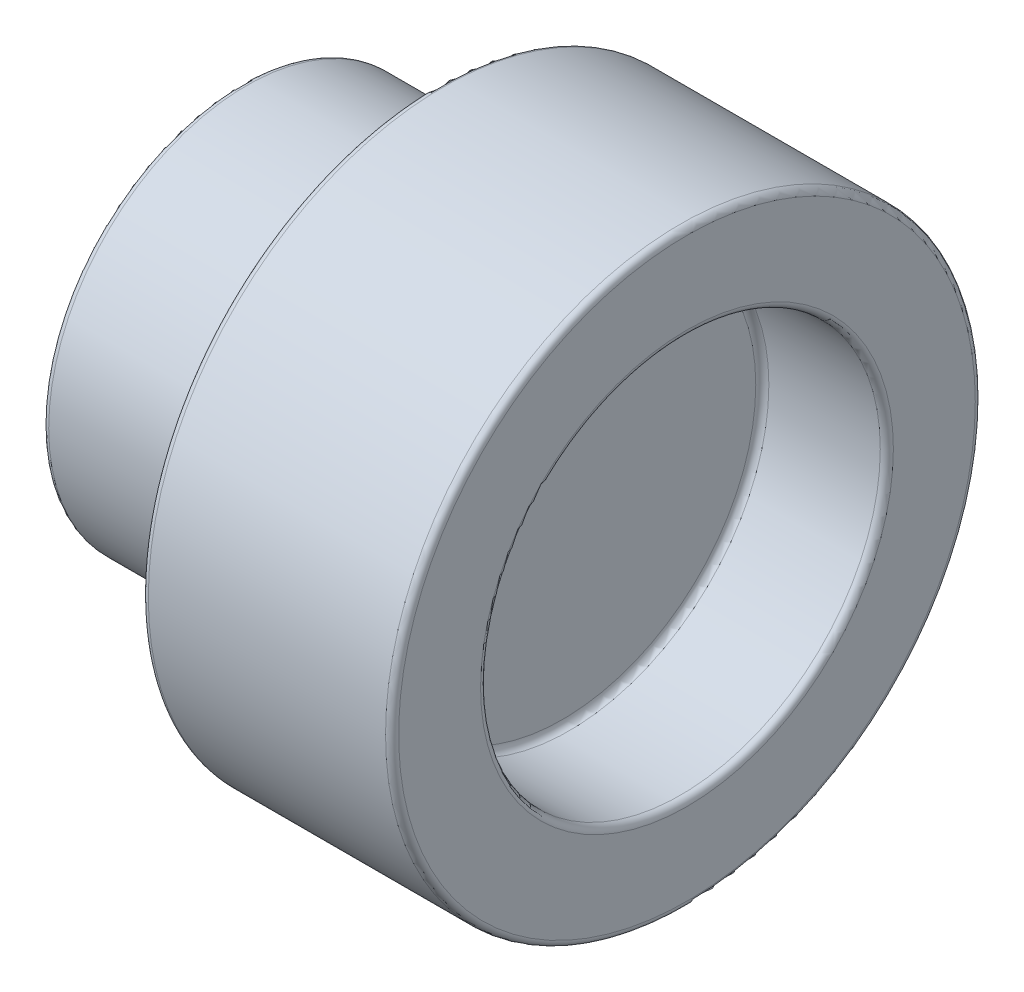
SolidWorks part; units mm, degrees
ref_plane "前视基准面" through (0, 0, 0) normal (0, 0, 1) x (1, 0, 0)
ref_plane "上视基准面" through (0, 0, 0) normal (0, 1, 0) x (1, 0, 0)
ref_plane "右视基准面" through (0, 0, 0) normal (1, 0, 0) x (0, 0, -1)
other "Configuration Table"
sketch "草图1" plane through (0, 0, 0) normal (1, 0, 0) x (0, 0, -1)
  circle A0 centre (0, 0) radius 4.5
  circle A1 centre (0, 0) radius 3.05
  dimension "D1" = 6.1
  dimension "D2" = 9
extrude "凸台-拉伸1" add sketch "草图1" along normal blind 3.82
sketch "草图2" plane through (0, 0, 0) normal (-1, 0, 0) x (0, 0, 1)
  circle A0 centre (0, 0) radius 3.05
  dimension "D1" = 6.1
extrude "凸台-拉伸2" add sketch "草图2" along normal blind 3 and the other way offset from surface 1.9 separate body other way up to face at (3.82, 0, -4.5)
sketch "草图3" plane through (-3, 0, 0) normal (-1, 0, 0) x (0, 0, 1)
  circle A0 centre (0, 0) radius 3.02
  circle A1 centre (0, 0) radius 3.05
  circle A2 centre (0, 0) radius 3.05
  dimension "D1" = 0
  dimension "D2" = 0.03
extrude "切除-拉伸1" cut sketch "草图3" against normal up to surface (3 mm away) up to face at (0, 0, -4.5)
fillet "圆角1" radius 0.1 3 edges at (3.82, 0, -3.05) (0, 0, -4.5) (3.82, 0, -4.5)
fillet "圆角2" radius 0.1 1 edges at (-3, 0, 3.02)
fillet "圆角3" radius 0.1 1 edges at (0, 0, -3.02)
combine bodies "组合1" operation type add bodies to combine 106 108
fillet "圆角4" radius 0.1 1 edges at (1.92, 0, -3.05)
